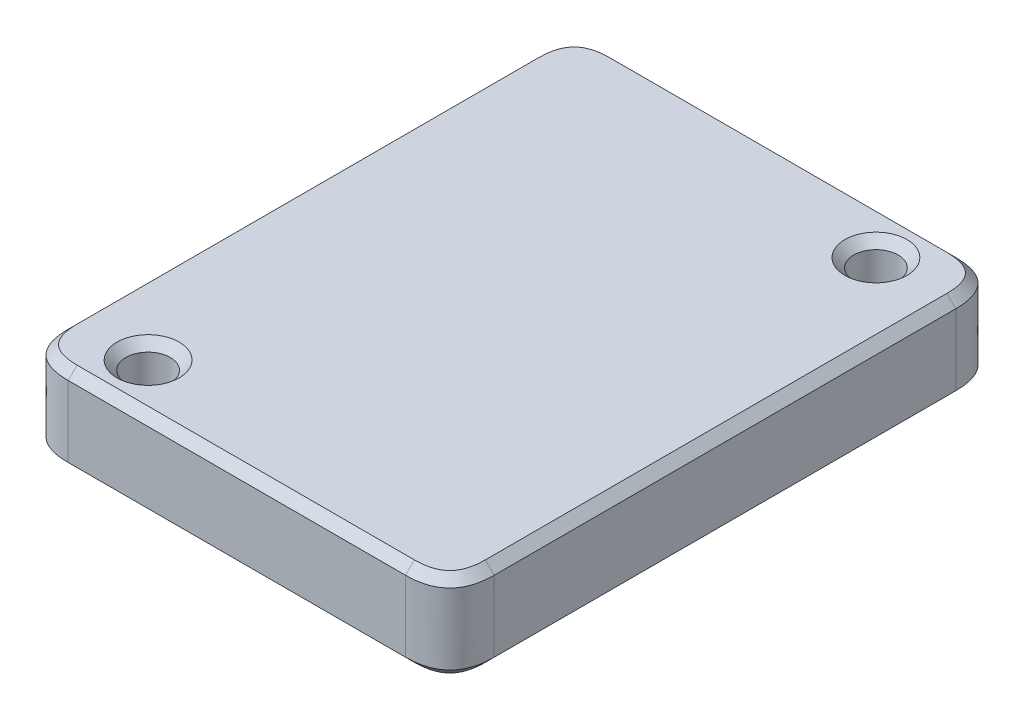
SolidWorks part; units mm, degrees
ref_plane "Front Plane" through (0, 0, 0) normal (0, 0, 1) x (1, 0, 0)
ref_plane "Top Plane" through (0, 0, 0) normal (0, 1, 0) x (1, 0, 0)
ref_plane "Right Plane" through (0, 0, 0) normal (1, 0, 0) x (0, 0, -1)
sketch "Sketch1" plane through (0, 0, 0) normal (0, 1, 0) x (1, 0, 0)
  line L1 (-24, 31) -> (24, 31)
  line L2 (-24, 31) -> (-24, -31)
  line L3 (-24, -31) -> (24, -31)
  line L4 (24, 31) -> (24, -31)
  line L5 (-24, 31) -> (24, -31) construction
  line L6 (-24, -31) -> (24, 31) construction
  point P0 (0, 0)
extrude "Boss-Extrude1" add sketch "Sketch1" along normal blind 10
sketch "Sketch2" plane through (0, 10, 0) normal (0, 1, 0) x (1, 0, 0)
  line L0 (24, -31) -> (24, 31) construction
  line L1 (24, 31) -> (-24, 31) construction
  line L2 (-24, 31) -> (-24, -31) construction
  line L3 (-24, -31) -> (24, -31) construction
  circle A0 centre (15.5, 25.5) radius 3.5
  circle A1 centre (-15.5, -25.5) radius 3.5
  dimension "D1" = 8.5
  dimension "D3" = 7
  dimension "D2" = 5.5
  dimension "D4" = 8.5
  dimension "D5" = 5.5
extrude "Cut-Extrude2" cut sketch "Sketch2" against normal blind 1 draft 45 contours A0 | A1
sketch "Sketch3" plane through (0, 10, 0) normal (0, 1, 0) x (1, 0, 0)
  circle A0 centre (-15.5, -25.5) radius 3.5
  circle A1 centre (15.5, 25.5) radius 3.5
sketch "Sketch4" plane through (0, 0, 0) normal (0, -1, 0) x (1, 0, 0)
  circle A0 centre (-15.5, 25.5) radius 3.5
  circle A1 centre (15.5, -25.5) radius 3.5
extrude "Cut-Extrude3" cut sketch "Sketch4" against normal blind 1 draft 45
sketch "Sketch5" plane through (0, 10, 0) normal (0, 1, 0) x (1, 0, 0)
  circle A0 centre (-15.5, -25.5) radius 2.5
  circle A1 centre (15.5, 25.5) radius 2.5
extrude "Cut-Extrude4" cut sketch "Sketch5" against normal through all contours A0 | A1
fillet "Fillet4" radius 5 1 edges at (-24, 5, -31) type face fillet first side face at (-24, 5, 0) second side face at (0, 5, -31) conic rho 0.5
fillet "Fillet5" radius 5 1 edges at (24, 5, -31) type face fillet first side face at (13.25, 3.75, -31) second side face at (24, 5, 0) conic rho 0.5
fillet "Fillet6" radius 5 1 edges at (24, 5, 31) type face fillet first side face at (24, 3.75, 16.75) second side face at (0, 5, 31) conic rho 0.5
fillet "Fillet7" radius 5 1 edges at (-24, 5, 31) type face fillet first side face at (-13.25, 3.75, 31) second side face at (-24, 6.25, -11.75) conic rho 0.5
chamfer "Chamfer4" distance 1 angle 45 8 edges
chamfer "Chamfer5" distance 1 angle 45 8 edges
